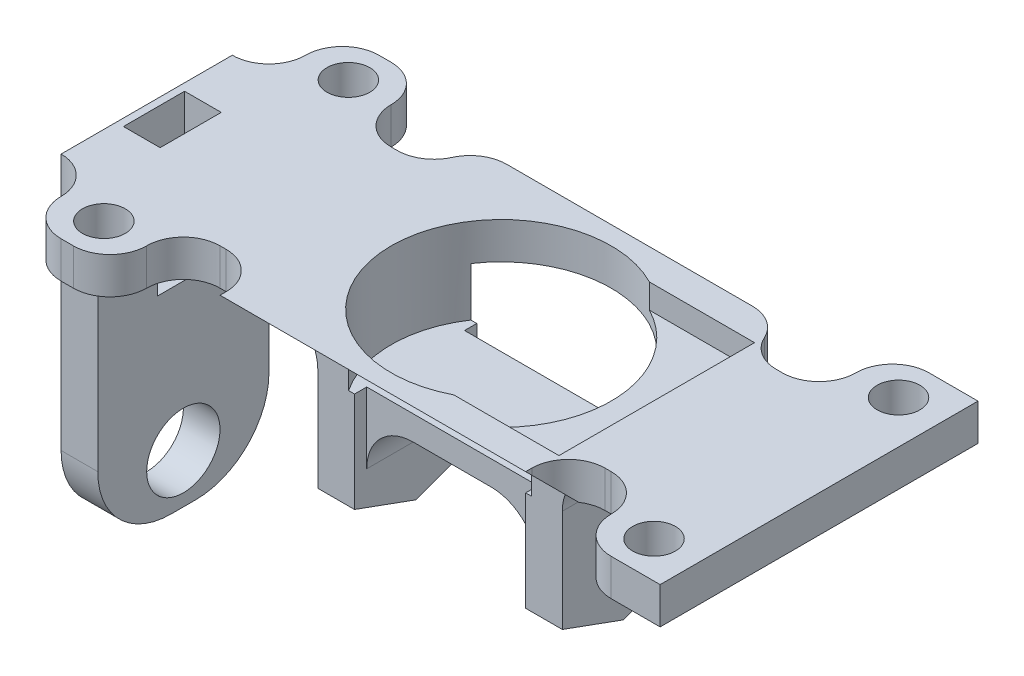
SolidWorks part; units mm, degrees
ref_plane "Front Plane" through (0, 0, 0) normal (0, 0, 1) x (1, 0, 0)
ref_plane "Top Plane" through (0, 0, 0) normal (0, 1, 0) x (1, 0, 0)
ref_plane "Right Plane" through (0, 0, 0) normal (1, 0, 0) x (0, 0, -1)
sketch "Sketch1" plane through (0, 0, 0) normal (0, 1, 0) x (1, 0, 0)
  line L1 (-1.5, 7) -> (1.5, 7)
  line L2 (-1.5, 7) -> (-1.5, -7)
  line L3 (-1.5, -7) -> (1.5, -7)
  line L4 (1.5, 7) -> (1.5, -7)
  line L5 (-1.5, 7) -> (1.5, -7) construction
  line L6 (-1.5, -7) -> (1.5, 7) construction
  point P0 (0, 0)
  dimension "D1" = 14
  dimension "D2" = 3
extrude "Boss-Extrude1" add sketch "Sketch1" along normal blind 27
sketch "Sketch2" plane through (-1.5, 0, 0) normal (-1, 0, 0) x (0, 0, 1)
  line L0 (-7, 0) -> (7, 0) construction
  circle A0 centre (0, 4) radius 3
  point P5 (0, 0)
  dimension "D1" = 6
  dimension "D2" = 4
extrude "Cut-Extrude1" cut sketch "Sketch2" against normal through all
sketch "Sketch3" plane through (1.5, 0, 0) normal (1, 0, 0) x (0, 0, -1)
  line L0 (7, 27) -> (7, 0) construction
  line L1 (-7, 27) -> (7, 27)
  line L2 (-7, 27) -> (-7, 24)
  line L3 (-7, 24) -> (7, 24)
  line L4 (7, 27) -> (7, 24)
  dimension "D1" = 3
extrude "Boss-Extrude2" add sketch "Sketch3" along normal blind 52
sketch "Sketch4" plane through (0, 24, 0) normal (0, -1, 0) x (1, 0, 0)
  line L0 (53.5, 7) -> (53.5, -7) construction
  line L1 (37.5, 5) -> (34.5, 5)
  line L2 (37.5, 5) -> (37.5, -5)
  line L3 (37.5, -5) -> (34.5, -5)
  line L4 (17.5, 5) -> (17.5, -5)
  line L5 (37.5, 5) -> (17.5, -5) construction
  line L6 (37.5, -5) -> (17.5, 5) construction
  line L7 (53.5, 7) -> (1.5, 7) construction
  line L8 (20.5, -5) -> (17.5, -5)
  line L10 (20.5, -5) -> (20.5, 5)
  line L12 (34.5, -5) -> (34.5, 5)
  line L13 (20.5, 5) -> (17.5, 5)
  point P0 (27.5, 0)
  point P8 (53.5, 0)
  point P11 (27.5, 7)
  dimension "D1" = 10
  dimension "D2" = 20
  dimension "D3" = 3
  dimension "D4" = 3
extrude "Boss-Extrude3" add sketch "Sketch4" along normal blind 14
chamfer "Chamfer1" distance 5 angle 20 4 edges at (36, 10, -5) (36, 10, 5) (19, 10, 5) (19, 10, -5) first distance on face at (36, 10, 0) first distance on face at (19, 10, 0)
ref_plane "Plane1" through (27.5, 0, 0) normal (-1, 0, 0) x (0, 0, 1)
sketch "Sketch6" plane through (0, 0, -7) normal (0, 0, -1) x (-1, 0, 0)
  line L0 (-53.5, 27) -> (1.5, 27) construction
  line L1 (-40, 27) -> (-15, 27)
  line L2 (-40, 27) -> (-40, 24)
  line L3 (-40, 24) -> (-15, 24)
  line L4 (-15, 27) -> (-15, 24)
  line L5 (-53.5, 24) -> (-1.5, 24) construction
  point P8 (-27.5, 24)
  point P9 (-27.5, 24)
  dimension "D1" = 25
extrude "Boss-Extrude5" add sketch "Sketch6" along normal blind 3.5
sketch "Sketch5" plane through (0, 0, 7) normal (0, 0, 1) x (1, 0, 0)
  line L0 (-1.5, 27) -> (53.5, 27) construction
  line L1 (1.5, 27) -> (8.5, 27)
  line L2 (1.5, 27) -> (1.5, 24)
  line L3 (1.5, 24) -> (8.5, 24)
  line L4 (8.5, 27) -> (8.5, 24)
  line L5 (53.5, 24) -> (1.5, 24) construction
  line L6 (27.5, 5.5) -> (27.5, -5.5) construction
  line L7 (53.5, 24) -> (46.5, 24)
  line L8 (46.5, 27) -> (46.5, 24)
  line L9 (53.5, 27) -> (46.5, 27)
  line L10 (53.5, 27) -> (53.5, 24)
  point P14 (5, 24)
  dimension "D1" = 7
  dimension "D2" = 22.5
extrude "Boss-Extrude4" add sketch "Sketch5" along normal blind 6
mirror "Mirror1" about plane through (0, 0, 0) normal (0, 0, 1) of "Boss-Extrude4", "Boss-Extrude5"
sketch "Sketch7" plane through (0, 27, 0) normal (0, 1, 0) x (1, 0, 0)
  line L0 (27.5, 5.5) -> (27.5, -5.5) construction
  circle A0 centre (27.5, 0) radius 9
  dimension "D1" = 18
extrude "Cut-Extrude2" cut sketch "Sketch7" against normal blind 7
chamfer "Chamfer2" distance 3 angle 45 1 edges at (27.5, 24, 10.5)
sketch "Sketch8" plane through (20.5, 0, 0) normal (1, 0, 0) x (0, 0, -1)
  line L0 (-5, 20) -> (5, 20) construction
  line L1 (4, 20) -> (-4, 20)
  line L2 (4, 20) -> (4, 18)
  line L3 (4, 18) -> (-4, 18)
  line L4 (-4, 20) -> (-4, 18)
  point P6 (0, 20)
  point P7 (0, 20)
  dimension "D1" = 2
  dimension "D2" = 8
extrude "Boss-Extrude6" add sketch "Sketch8" along normal up to vertex (14 mm away) up to point (34.5, 20, 5)
sketch "Sketch9" plane through (0, 27, 0) normal (0, 1, 0) x (1, 0, 0)
  line L1 (40.2231, 8) -> (31.6231, 8)
  line L2 (40.2231, 8) -> (40.2231, -8)
  line L3 (40.2231, -8) -> (31.6231, -8)
  line L4 (31.6231, 8) -> (31.6231, -8)
  circle A0 centre (27.5, 0) radius 9 construction
  dimension "D1" = 16
  dimension "D2" = 8.6
extrude "Cut-Extrude3" cut sketch "Sketch9" against normal blind 2
sketch "Sketch10" plane through (0, 27, 0) normal (0, 1, 0) x (1, 0, 0)
  line L0 (8.5, -13) -> (1.5, -13) construction
  line L1 (1.5, -13) -> (1.5, -7) construction
  line L2 (1.5, 13) -> (1.5, 7) construction
  line L3 (8.5, 13) -> (1.5, 13) construction
  line L4 (53.5, -13) -> (46.5, -13) construction
  circle A0 centre (5, -10) radius 1.75
  circle A1 centre (50, -10) radius 1.75
  circle A2 centre (50, 10) radius 1.75
  circle A3 centre (5, 10) radius 1.75
  point P5 (5, -13)
  point P8 (1.5, -10)
  point P18 (1.5, 10)
  point P23 (5, 13)
  point P27 (50, -13)
  dimension "D1" = 3.5
  dimension "D2" = 2
  dimension "D3" = 2
extrude "Cut-Extrude4" cut sketch "Sketch10" against normal up to next
sketch "Sketch11" plane through (0, 27, 0) normal (0, 1, 0) x (1, 0, 0)
  line L0 (1.5, -7) -> (1.5, 7) construction
  line L1 (-0.3, 2.1) -> (1.5, 2.1)
  line L2 (-0.3, 2.1) -> (-0.3, -2.1)
  line L3 (-0.3, -2.1) -> (1.5, -2.1)
  line L4 (1.5, 2.1) -> (1.5, -2.1)
  line L5 (-0.3, 2.1) -> (1.5, -2.1) construction
  line L6 (-0.3, -2.1) -> (1.5, 2.1) construction
  point P0 (0.6, 0)
  dimension "D1" = 1.8
  dimension "D2" = 0
  dimension "D3" = 4.2
extrude "Cut-Extrude5" cut sketch "Sketch11" against normal blind 11
fillet "Fillet1" radius 3 10 edges at (46.5, 25.5, 7) (40, 24.5, 7) (15, 25.5, 7) (8.5, 25.5, 7) (1.5, 25.5, 7) (1.5, 25.5, -7) (8.5, 25.5, -7) (15, 25.5, -7) (46.5, 25.5, -7) (40, 24.5, -7)
fillet "Fillet2" radius 3 8 edges at (46.5, 25.5, 13) (46.5, 25.5, -13) (40, 25.5, -10.5) (15, 25.5, -10.5) (8.5, 25.5, 13) (1.5, 25.5, 13) (1.5, 25.5, -13) (8.5, 25.5, -13)
fillet "Fillet3" radius 3.8 6 edges at (37.5, 24, 0) (20.5, 18, 0) (34.5, 18, 0) (17.5, 24, 0) (1.5, 24, 4.55) (1.5, 24, -4.55)
fillet "Fillet4" radius 6 2 edges at (0, 0, -7) (0, 0, 7)
sketch "Sketch12" plane through (0, 27, 0) normal (0, 1, 0) x (1, 0, 0)
  line L0 (-0.3, -2.1) -> (1.5, -2.1) construction
  line L1 (-0.9, 2.5) -> (2.1, 2.5)
  line L2 (-0.9, 2.5) -> (-0.9, -2.5)
  line L3 (-0.9, -2.5) -> (2.1, -2.5)
  line L4 (2.1, 2.5) -> (2.1, -2.5)
  line L5 (-0.9, 2.5) -> (2.1, -2.5) construction
  line L6 (-0.9, -2.5) -> (2.1, 2.5) construction
  line L8 (1.5, -2.1) -> (1.5, 2.1) construction
  point P0 (0.6, 0)
  point P5 (0, 0)
  point P8 (0.6, -2.1)
  point P9 (0, 0)
  point P10 (2.1, 0)
  point P13 (1.5, 0)
  dimension "D1" = 5
  dimension "D2" = 3
extrude "Cut-Extrude6" cut sketch "Sketch12" against normal blind 3
equation "\"D4@Sketch4\"=\"D3@Sketch4\""
